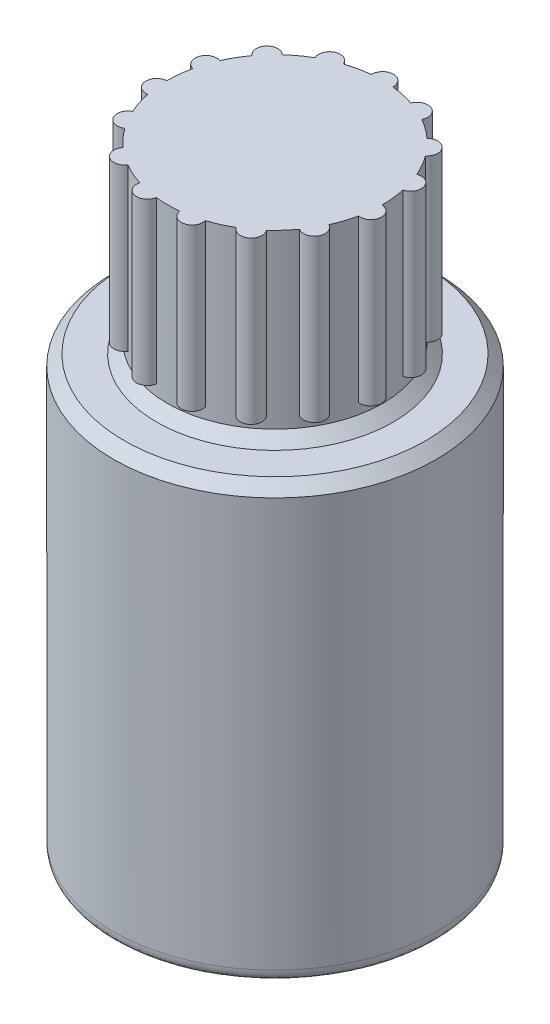
SolidWorks part; units mm, degrees
ref_plane "Front Plane" through (0, 0, 0) normal (0, 0, 1) x (1, 0, 0)
ref_plane "Top Plane" through (0, 0, 0) normal (0, 1, 0) x (1, 0, 0)
ref_plane "Right Plane" through (0, 0, 0) normal (1, 0, 0) x (0, 0, -1)
sketch "Sketch1" plane through (0, 0, 0) normal (0, 0, 1) x (1, 0, 0)
  line L0 (15, 0) -> (15, 40)
  line L1 (15, 40) -> (10, 40)
  line L2 (10, 40) -> (10, 57)
  line L3 (10, 57) -> (0, 57)
  line L4 (12, 0) -> (12, 37)
  line L5 (12, 37) -> (0, 37)
  line L6 (0, 57) -> (0, 37)
  line L7 (12, 37) -> (10, 37) construction
  line L8 (12, 0) -> (15, 0)
  point P9 (0, 0)
  dimension "D1" = 3
  dimension "D2" = 12
  dimension "D3" = 10
  dimension "D4" = 40
  dimension "D5" = 20
revolve "Revolve1" add sketch "Sketch1" angle 360 about L6
ref_axis "Axis1" through (0, 0, 0) along (0, 1, 0)
chamfer "Chamfer1" distance 1 angle 45 3 edges at (-10, 40, 0) (-15, 40, 0) (-12, 0, 0)
fillet "Fillet1" radius 1 1 edges at (-15, 0, 0) curvature continuous yes
sketch "Sketch2" plane through (0, 57, 0) normal (0, 1, 0) x (1, 0, 0)
  circle A0 centre (0, 10) radius 1
  circle A1 centre (0, 0) radius 10 construction
  circle A2 centre (0, 0) radius 10 construction
  point P6 (0, 0)
  dimension "D1" = 2
extrude "Boss-Extrude1" add sketch "Sketch2" against normal blind 15
pattern_circular "CirPattern1" count 15 over 360 about axis through (0, 0, 0) along (0, 1, 0) of "Boss-Extrude1"
